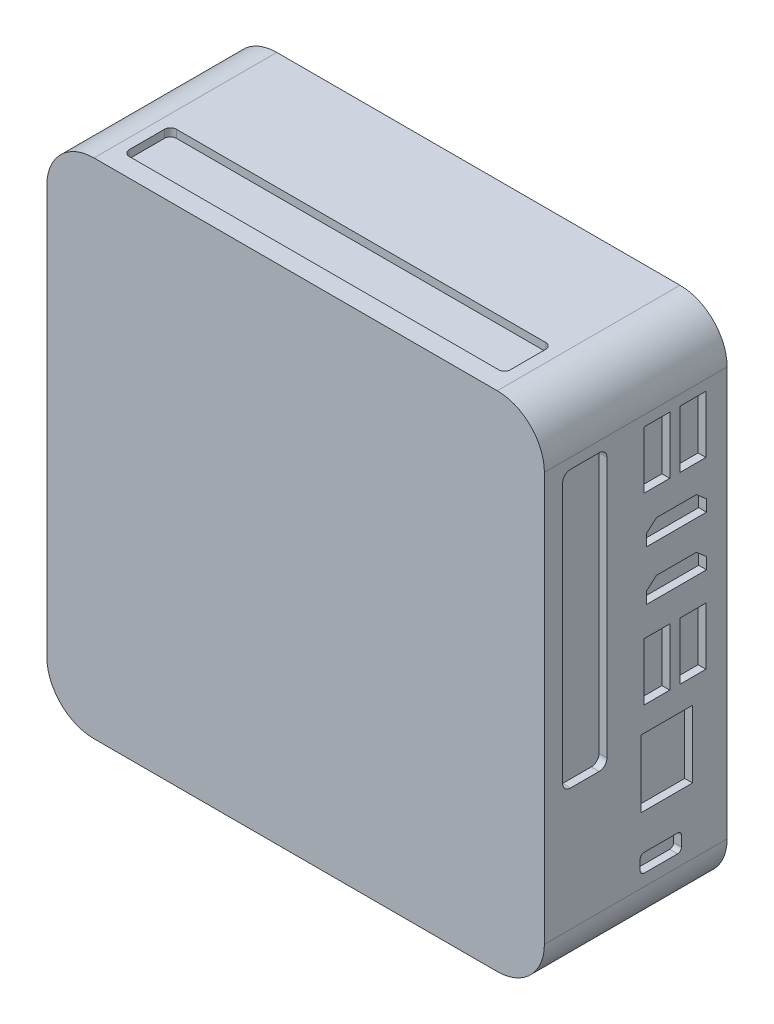
SolidWorks part; units mm, degrees
ref_plane "Płaszczyzna przednia" through (0, 0, 0) normal (0, 0, 1) x (1, 0, 0)
ref_plane "Płaszczyzna górna" through (0, 0, 0) normal (0, 1, 0) x (1, 0, 0)
ref_plane "Płaszczyzna prawa" through (0, 0, 0) normal (1, 0, 0) x (0, 0, -1)
sketch "Szkic1" plane through (0, 0, 0) normal (0, 0, 1) x (1, 0, 0)
  line L1 (-51.3, -64) -> (51.3, -64)
  line L2 (-63.3, -52) -> (-63.3, 52)
  line L3 (-51.3, 64) -> (51.3, 64)
  line L4 (63.3, -52) -> (63.3, 52)
  line L5 (-63.3, -64) -> (63.3, 64) construction
  line L6 (-63.3, 64) -> (63.3, -64) construction
  arc A0 (-51.3, -64) -> (-63.3, -52) centre (-51.3, -52) cw
  arc A1 (51.3, -64) -> (63.3, -52) centre (51.3, -52) ccw
  arc A2 (51.3, 64) -> (63.3, 52) centre (51.3, 52) cw
  arc A3 (-63.3, 52) -> (-51.3, 64) centre (-51.3, 52) cw
  point P0 (0, 0)
  dimension "D3" = 12
  dimension "D1" = 128
  dimension "D2" = 126.6
extrude "Dodanie-wyciągnięcie1" add sketch "Szkic1" along normal blind 46.5
sketch "Szkic2" plane through (0, 64, 0) normal (0, 1, 0) x (1, 0, 0)
  line L0 (-48.65, -31.2) -> (-48.65, -40.2)
  line L1 (-51.3, -46.5) -> (-51.3, 0) construction
  line L2 (-47.15, -29.7) -> (46.85, -29.7)
  line L3 (48.35, -31.2) -> (48.35, -40.2)
  line L4 (46.85, -41.7) -> (-47.15, -41.7)
  line L5 (51.3, -46.5) -> (-51.3, -46.5) construction
  arc A0 (48.35, -40.2) -> (46.85, -41.7) centre (46.85, -40.2) cw
  arc A1 (46.85, -29.7) -> (48.35, -31.2) centre (46.85, -31.2) cw
  arc A2 (-48.65, -40.2) -> (-47.15, -41.7) centre (-47.15, -40.2) ccw
  arc A3 (-48.65, -31.2) -> (-47.15, -29.7) centre (-47.15, -31.2) cw
  point P10 (48.35, -29.7)
  point P13 (-48.65, -41.7)
  point P16 (-48.65, -29.7)
  dimension "D4" = 1.5
  dimension "D1" = 12
  dimension "D2" = 2.65
  dimension "D3" = 97
  dimension "D5" = 4.8
extrude "Wytnij-wyciągnięcie1" cut sketch "Szkic2" against normal blind 2
sketch "Szkic3" plane through (-63.3, 0, 0) normal (-1, 0, 0) x (0, 0, 1)
  line L0 (29.5, -45.8) -> (38.5, -45.8)
  line L1 (46.5, -52) -> (0, -52) construction
  line L2 (28, -44.3) -> (28, 43.7)
  line L3 (29.5, 45.2) -> (38.5, 45.2)
  line L4 (40, 43.7) -> (40, -44.3)
  line L5 (46.5, 52) -> (46.5, -52) construction
  line L6 (15.3777, -23) -> (15.3777, -28.8) construction
  line L7 (17.0277, -23) -> (17.0277, -28.8)
  line L8 (13.7277, -23) -> (13.7277, -28.8)
  line L9 (15.3777, -3.9) -> (15.3777, -9.7) construction
  line L10 (17.0277, -3.9) -> (17.0277, -9.7)
  line L11 (13.7277, -3.9) -> (13.7277, -9.7)
  line L13 (13.3777, 32.6) -> (17.3777, 32.6)
  line L14 (12.3777, 31.6) -> (12.3777, 23.1)
  line L15 (13.3777, 22.1) -> (17.3777, 22.1)
  line L16 (18.3777, 31.6) -> (18.3777, 23.1)
  arc A0 (28, 43.7) -> (29.5, 45.2) centre (29.5, 43.7) cw
  arc A1 (38.5, 45.2) -> (40, 43.7) centre (38.5, 43.7) cw
  arc A2 (38.5, -45.8) -> (40, -44.3) centre (38.5, -44.3) ccw
  arc A3 (29.5, -45.8) -> (28, -44.3) centre (29.5, -44.3) cw
  arc A4 (17.0277, -23) -> (13.7277, -23) centre (15.3777, -23) ccw
  arc A5 (13.7277, -28.8) -> (17.0277, -28.8) centre (15.3777, -28.8) ccw
  arc A6 (17.0277, -3.9) -> (13.7277, -3.9) centre (15.3777, -3.9) ccw
  arc A7 (13.7277, -9.7) -> (17.0277, -9.7) centre (15.3777, -9.7) ccw
  circle A8 centre (15.3777, 10.1) radius 3.25
  arc A9 (13.3777, 32.6) -> (12.3777, 31.6) centre (13.3777, 31.6) ccw
  arc A10 (17.3777, 32.6) -> (18.3777, 31.6) centre (17.3777, 31.6) cw
  arc A11 (17.3777, 22.1) -> (18.3777, 23.1) centre (17.3777, 23.1) ccw
  arc A12 (12.3777, 23.1) -> (13.3777, 22.1) centre (13.3777, 23.1) ccw
  point P10 (28, 45.2)
  point P15 (40, -45.8)
  point P18 (28, -45.8)
  point P21 (15.3777, -25.9)
  point P26 (15.3777, -6.8)
  point P41 (12.3777, 32.6)
  point P46 (18.3777, 22.1)
  point P49 (12.3777, 22.1)
  dimension "D5" = 1.5
  dimension "D8" = 1.65
  dimension "D9" = 1.65
  dimension "D12" = 6.5
  dimension "D18" = 1
  dimension "D1" = 12
  dimension "D2" = 6.2
  dimension "D3" = 91
  dimension "D4" = 6.5
  dimension "D6" = 23.2
  dimension "D7" = 5.8
  dimension "D10" = 5.8
  dimension "D11" = 13.3
  dimension "D13" = 14
  dimension "D14" = 12
  dimension "D15" = 6
  dimension "D16" = 3
  dimension "D17" = 10.5
extrude "Wytnij-wyciągnięcie2" cut sketch "Szkic3" against normal blind 2 contours A3 L0 A2 L4 A1 L3 A0 L2 | L8 A5 L7 A4 | L11 A7 L10 A6 | A8 region at (-63.3, -0.3, 34) region at (-63.3, -25.9, 15.3777) region at (-63.3, -6.8, 15.3777) region at (-63.3, 10.1, 15.3777)
extrude "Dodanie-wyciągnięcie2" add sketch "Szkic3<3>" along normal blind 2 contours L14 A12 L15 A11 L16 A10 L13 A9 region at (-63.3, 27.35, 15.3777)
sketch "Szkic3<3>" plane through (-63.3, 0, 0) normal (-1, 0, 0) x (0, 0, 1) same geometry as "Szkic3"
mirror "Lustro1" about plane through (0, 0, 0) normal (0, 1, 0) of "Wytnij-wyciągnięcie1"
sketch "Szkic5" plane through (63.3, 0, 0) normal (1, 0, 0) x (0, 0, -1)
  line L0 (-39.86, 49.36) -> (-32.58, 49.36)
  line L1 (-46.5, 52) -> (0, 52) construction
  line L2 (-41.86, 47.36) -> (-41.86, -18.86)
  line L3 (-39.86, -20.86) -> (-32.58, -20.86)
  line L4 (-30.58, -18.86) -> (-30.58, 47.36)
  line L5 (-46.5, -52) -> (-46.5, 52) construction
  line L6 (-46.5, -52) -> (0, -52) construction
  line L7 (-21.12, -44.41) -> (-12.62, -44.41)
  line L8 (-22.12, -45.41) -> (-22.12, -48)
  line L9 (-21.12, -49) -> (-12.62, -49)
  line L10 (-11.62, -45.41) -> (-11.62, -48)
  line L11 (0, -52) -> (0, 52) construction
  line L12 (-12.01, -11.93) -> (-5.4, -11.93)
  line L13 (-21.92, -35.29) -> (-8.8, -35.29)
  line L14 (-21.92, -35.29) -> (-21.92, -18.16)
  line L15 (-21.92, -18.16) -> (-8.8, -18.16)
  line L16 (-8.8, -35.29) -> (-8.8, -18.16)
  line L17 (-12.01, -11.93) -> (-12.01, 2.67)
  line L18 (-12.01, 2.67) -> (-5.4, 2.67)
  line L19 (-5.4, 2.67) -> (-5.4, -11.93)
  line L20 (-21.21, -11.93) -> (-14.6, -11.93)
  line L21 (-14.6, 2.67) -> (-14.6, -11.93)
  line L22 (-21.21, 2.67) -> (-14.6, 2.67)
  line L23 (-21.21, -11.93) -> (-21.21, 2.67)
  line L24 (-20.57, 9.9) -> (-5.24, 9.9)
  line L25 (-5.24, 9.9) -> (-5.24, 12.83)
  line L27 (-7.82, 15.06) -> (-17.99, 15.06)
  line L28 (-17.99, 15.06) -> (-20.57, 12.83)
  line L29 (-20.57, 12.83) -> (-20.57, 9.9)
  line L30 (-7.82, 15.06) -> (-5.24, 12.83)
  line L31 (-7.82, 27.77) -> (-5.24, 25.54)
  line L32 (-5.24, 22.61) -> (-5.24, 25.54)
  line L33 (-20.57, 22.61) -> (-5.24, 22.61)
  line L34 (-20.57, 25.54) -> (-20.57, 22.61)
  line L35 (-17.99, 27.77) -> (-20.57, 25.54)
  line L36 (-7.82, 27.77) -> (-17.99, 27.77)
  line L37 (-21.21, 34.74) -> (-14.6, 34.74)
  line L38 (-14.6, 49.34) -> (-14.6, 34.74)
  line L39 (-21.21, 49.34) -> (-14.6, 49.34)
  line L40 (-21.21, 34.74) -> (-21.21, 49.34)
  line L41 (-5.4, 49.34) -> (-5.4, 34.74)
  line L42 (-12.01, 34.74) -> (-5.4, 34.74)
  line L43 (-12.01, 34.74) -> (-12.01, 49.34)
  line L44 (-12.01, 49.34) -> (-5.4, 49.34)
  arc A0 (-41.86, -18.86) -> (-39.86, -20.86) centre (-39.86, -18.86) ccw
  arc A1 (-32.58, -20.86) -> (-30.58, -18.86) centre (-32.58, -18.86) ccw
  arc A2 (-32.58, 49.36) -> (-30.58, 47.36) centre (-32.58, 47.36) cw
  arc A3 (-41.86, 47.36) -> (-39.86, 49.36) centre (-39.86, 47.36) cw
  arc A4 (-12.62, -44.41) -> (-11.62, -45.41) centre (-12.62, -45.41) cw
  arc A5 (-12.62, -49) -> (-11.62, -48) centre (-12.62, -48) ccw
  arc A6 (-22.12, -48) -> (-21.12, -49) centre (-21.12, -48) ccw
  arc A7 (-21.12, -44.41) -> (-22.12, -45.41) centre (-21.12, -45.41) ccw
  point P10 (-41.86, -20.86)
  point P15 (-30.58, 49.36)
  point P18 (-41.86, 49.36)
  point P29 (-11.62, -44.41)
  point P32 (-11.62, -49)
  dimension "D5" = 2
  dimension "D10" = 1
  dimension "D1" = 11.28
  dimension "D2" = 2.64
  dimension "D3" = 70.22
  dimension "D4" = 4.64
  dimension "D6" = 3
  dimension "D7" = 10.5
  dimension "D8" = 11.62
  dimension "D9" = 4.59
  dimension "D11" = 9.12
  dimension "D12" = 13.12
  dimension "D13" = 8.8
  dimension "D14" = 17.13
  dimension "D15" = 6.61
  dimension "D16" = 6.23
  dimension "D17" = 14.6
  dimension "D18" = 5.4
  dimension "D20" = 2.59
  dimension "D21" = 7.23
  dimension "D22" = 15.33
  dimension "D23" = 5.24
  dimension "D24" = 5.16
  dimension "D25" = 2.93
  dimension "D26" = 10.17
  dimension "D27" = 2.58
  dimension "D28" = 2.23
  dimension "D19" = 2
  dimension "D29" = 2
  dimension "D30" = 2
extrude "Wytnij-wyciągnięcie3" cut sketch "Szkic5" against normal blind 2
